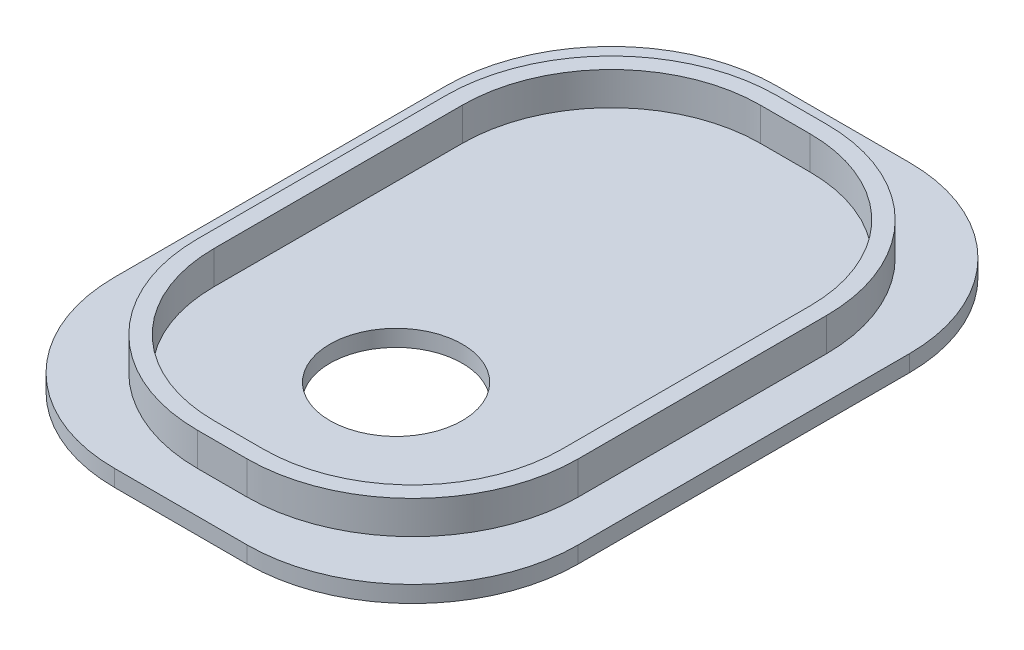
SolidWorks part; units mm, degrees
ref_plane "Front Plane" through (0, 0, 0) normal (0, 0, 1) x (1, 0, 0)
ref_plane "Top Plane" through (0, 0, 0) normal (0, 1, 0) x (1, 0, 0)
ref_plane "Right Plane" through (0, 0, 0) normal (1, 0, 0) x (0, 0, -1)
sketch "Sketch1" plane through (0, 0, 0) normal (0, 1, 0) x (1, 0, 0)
  line L0 (4, 27) -> (-4, 27)
  line L1 (-14, -3) -> (-14, 17)
  line L2 (4, -13) -> (-4, -13)
  line L3 (14, -3) -> (14, 17)
  line L4 (-11.5, 14.5) -> (-11.5, -0.5)
  line L5 (-1.5, 24.5) -> (1.5, 24.5)
  line L6 (11.5, 14.5) -> (11.5, -0.5)
  line L7 (-1.5, -10.5) -> (1.5, -10.5)
  line L8 (-10.5, 14.5) -> (-10.5, -0.5)
  line L9 (-1.5, -9.5) -> (1.5, -9.5)
  line L10 (10.5, 14.5) -> (10.5, -0.5)
  line L11 (-1.5, 23.5) -> (1.5, 23.5)
  arc A0 (-4, 27) -> (-14, 17) centre (-4, 17) ccw
  arc A1 (-14, -3) -> (-4, -13) centre (-4, -3) ccw
  arc A2 (4, -13) -> (14, -3) centre (4, -3) ccw
  arc A3 (14, 17) -> (4, 27) centre (4, 17) ccw
  arc A4 (-1.5, 24.5) -> (-11.5, 14.5) centre (-1.5, 14.5) ccw
  arc A5 (11.5, 14.5) -> (1.5, 24.5) centre (1.5, 14.5) ccw
  arc A6 (1.5, -10.5) -> (11.5, -0.5) centre (1.5, -0.5) ccw
  arc A7 (-11.5, -0.5) -> (-1.5, -10.5) centre (-1.5, -0.5) ccw
  circle A8 centre (0, 0) radius 9.5
  arc A9 (-10.5, -0.5) -> (-1.5, -9.5) centre (-1.5, -0.5) ccw
  arc A10 (1.5, -9.5) -> (10.5, -0.5) centre (1.5, -0.5) ccw
  arc A11 (10.5, 14.5) -> (1.5, 23.5) centre (1.5, 14.5) ccw
  arc A12 (-1.5, 23.5) -> (-10.5, 14.5) centre (-1.5, 14.5) ccw
  dimension "D1" = 1
extrude "Boss-Extrude1" add sketch "Sketch1" along normal blind 2 contours L4 A7 L7 A6 L6 A5 L5 A4 A12 L11 A11 L10 A10 L9 A9 L8 region at (-8.2749, 0, -21.2749)
extrude "Boss-Extrude3" add sketch "Sketch1<4>" against normal blind 1 contours L3 A3 L0 A0 L1 A1 L2 A2 A7 L4 A4 L5 A5 L6 A6 L7 | L4 A7 L7 A6 L6 A5 L5 A4 A12 L11 A11 L10 A10 L9 A9 L8 | L11 A12 L8 A9 L9 A8 A10 L10 A11 | A8 region at (10.7258, 0, -23.7258) region at (-8.2749, 0, -21.2749) region at (0, 0, 0) region at (0, 0, -12.8384)
sketch "Sketch1<4>" plane through (0, 0, 0) normal (0, 1, 0) x (1, 0, 0) same geometry as "Sketch1"
sketch "Sketch2" plane through (0, 0, 0) normal (0, 1, 0) x (1, 0, 0)
  circle A0 centre (0, 0) radius 4
  dimension "D1" = 8
extrude "Cut-Extrude1" cut sketch "Sketch2" against normal through all both and the other way through all
